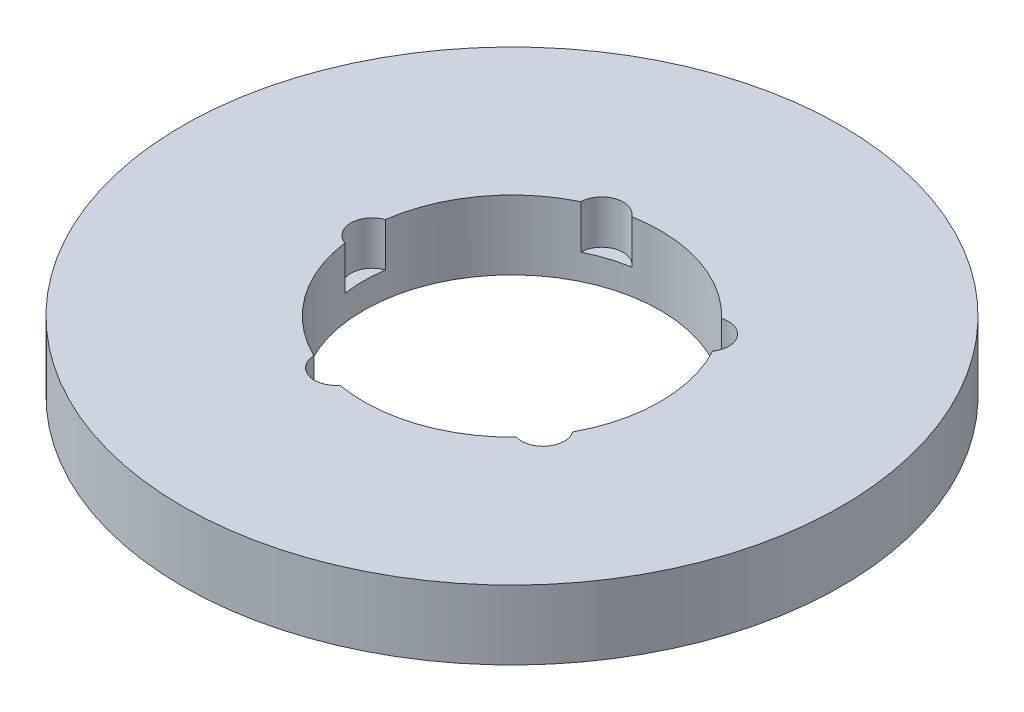
SolidWorks part; units mm, degrees
ref_plane "Front Plane" through (0, 0, 0) normal (0, 0, 1) x (1, 0, 0)
ref_plane "Top Plane" through (0, 0, 0) normal (0, 1, 0) x (1, 0, 0)
ref_plane "Right Plane" through (0, 0, 0) normal (1, 0, 0) x (0, 0, -1)
sketch "Sketch1" plane through (0, 0, 0) normal (0, 1, 0) x (1, 0, 0)
  circle A0 centre (0, 0) radius 100
  dimension "FLANGE_OD" = 200
extrude "Boss-Extrude1" add sketch "Sketch1" along normal blind 21
sketch "Sketch2" plane through (0, 0, 0) normal (0, 1, 0) x (1, 0, 0)
  circle A0 centre (0, 0) radius 45
  dimension "BORE_D" = 90
extrude "Cut-Extrude1" cut sketch "Sketch2" along normal through all
sketch "Sketch3" plane through (0, 21, 0) normal (0, 1, 0) x (1, 0, 0)
  circle A0 centre (0, 0) radius 42.4122 construction
  circle A1 centre (-42.4122, 0) radius 6.5102
  dimension "BOLT_D" = 13.0204
  dimension "BOLT_PCD" = 84.8245
extrude "Cut-Extrude2" cut sketch "Sketch3" against normal blind 13.2415
pattern_circular "CirPattern1" count 5 over 360 about axis through (0, 0, 0) along (0, 1, 0) of "Cut-Extrude2"
